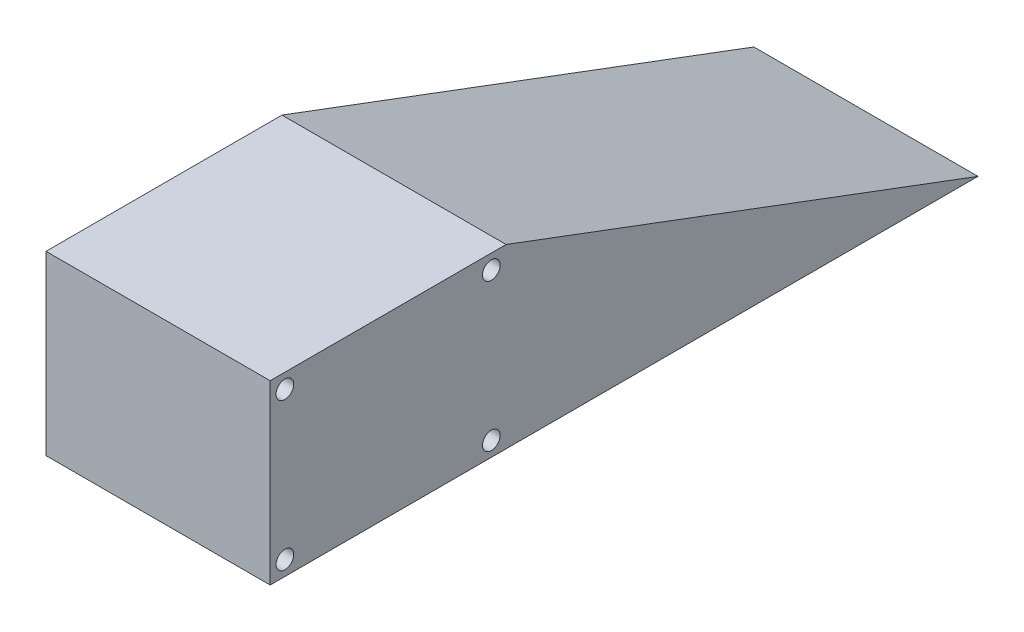
SolidWorks part; units mm, degrees
ref_plane "Front Plane" through (0, 0, 0) normal (0, 0, 1) x (1, 0, 0)
ref_plane "Top Plane" through (0, 0, 0) normal (0, 1, 0) x (1, 0, 0)
ref_plane "Right Plane" through (0, 0, 0) normal (1, 0, 0) x (0, 0, -1)
sketch "Sketch1" plane through (0, 0, 0) normal (1, 0, 0) x (0, 0, -1)
  line L0 (17.5, 12.5) -> (17.5, -12.5) construction
  line L1 (-20, 15) -> (20, 15)
  line L2 (-20, 15) -> (-20, -15)
  line L3 (-20, -15) -> (20, -15)
  line L4 (20, 15) -> (20, -15) construction
  line L5 (-20, 15) -> (20, -15) construction
  line L6 (-20, -15) -> (20, 15) construction
  line L7 (-17.5, -12.5) -> (17.5, -12.5) construction
  line L8 (-17.5, 12.5) -> (-17.5, -12.5) construction
  line L9 (-17.5, 12.5) -> (17.5, 12.5) construction
  line L10 (20, 15) -> (100, -15)
  line L11 (100, -15) -> (20, -15)
  point P0 (0, 0)
  point P11 (-17.5, 12.5)
  point P12 (17.5, 12.5)
  point P13 (17.5, -12.5)
  point P14 (-17.5, -12.5)
  point P16 (17.5, 12.5)
  point P17 (17.5, -12.5)
  point P18 (-17.5, -12.5)
  point P19 (-17.5, 12.5)
  point P20 (17.5, -12.5)
  point P21 (17.5, 12.5)
  point P22 (-17.5, -12.5)
  point P23 (-17.5, 12.5)
  dimension "D1" = 30
  dimension "D2" = 40
  dimension "D4" = 80
  dimension "D3" = 2.5
extrude "Boss-Extrude1" add sketch "Sketch1" along normal blind 38
ref_plane "Plane1" through (78, 0, 0) normal (1, 0, 0) x (0, 0, -1)
ref_plane "Plane2" through (39, 0, 0) normal (-1, 0, 0) x (0, 0, 1)
sketch "Sketch3" plane through (0, 0, 0) normal (-1, 0, 0) x (0, 0, 1)
  line L0 (-20, 15) -> (-20, -15) construction
  line L1 (20, -15) -> (-100, -15) construction
  line L2 (20, 15) -> (20, -15) construction
  line L4 (-20, 15) -> (20, 15) construction
  point P5 (-17.5, 12.5)
  point P6 (-17.5, -12.5)
  point P7 (17.5, -12.5)
  point P8 (17.5, 12.5)
  point P13 (0, 0)
  dimension "D1" = 2.5
  dimension "D2" = 2.5
  dimension "D3" = 2.5
  dimension "D4" = 2.5
  dimension "D5" = 2.5
  dimension "D6" = 2.5
  dimension "D7" = 2.5
  dimension "D8" = 2.5
hole_wizard "Ø3.0 (3) Diameter Hole1" positions "Sketch3" profile "Sketch4" hole size "Ø3.0" standard "ANSI Metric" end condition through all
sketch "Sketch4" plane through (0, 12.5, 17.5) normal (0, 1, 0) x (0, 0, 1)
  line L0 (0, 0) -> (0, 38)
  line L1 (0, 38) -> (1.5, 38)
  line L2 (1.5, 38) -> (1.5, 0.025)
  line L3 (1.5, 0.025) -> (1.525, 0)
  line L5 (1.525, 0) -> (0, 0)
  line L6 (-1.5, 0.025) -> (-1.525, 0) construction
  line L11 (0, -6.35) -> (0, 107.95) construction
  dimension "Thru Hole Dia." = 3
  dimension "Thru Hole Depth" = 38
  dimension "Near C'Sink Dia." = 3.05
  dimension "Near C'Sink Angle" = 90
